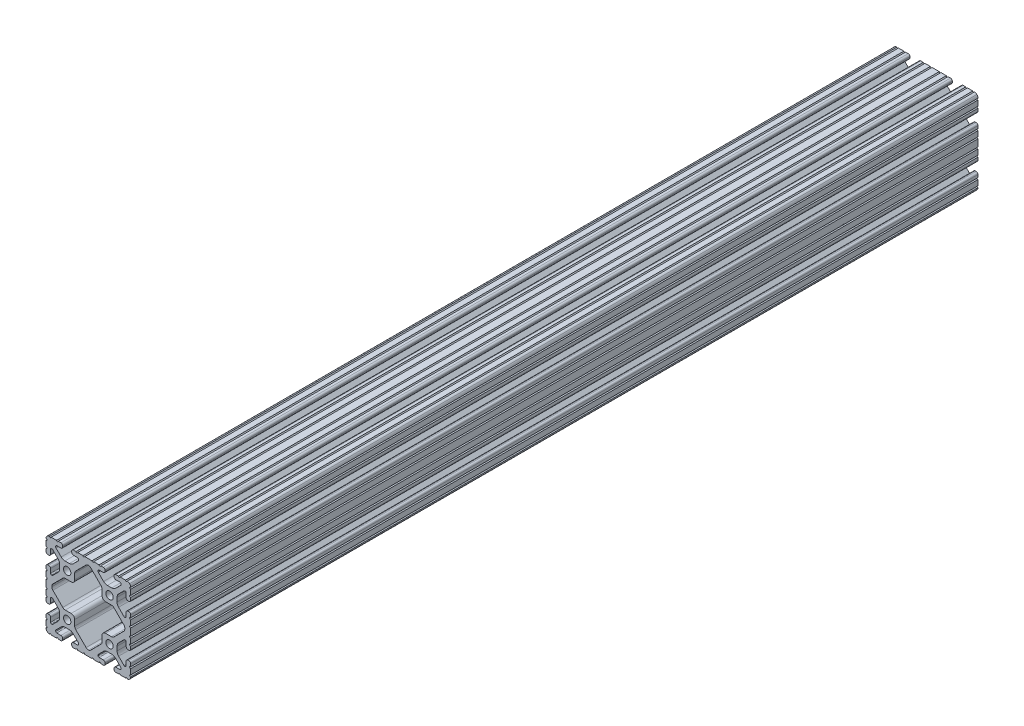
SolidWorks part; units mm, degrees
ref_plane "Front Plane" through (0, 0, 0) normal (0, 0, 1) x (1, 0, 0)
ref_plane "Top Plane" through (0, 0, 0) normal (0, 1, 0) x (1, 0, 0)
ref_plane "Right Plane" through (0, 0, 0) normal (1, 0, 0) x (0, 0, -1)
sketch "Sketch1" plane through (0, 0, 0) normal (0, 0, 1) x (1, 0, 0)
  line L0 (0, 38.1) -> (0, -38.1) construction
  line L1 (-38.1, -38.1) -> (38.1, -38.1) construction
  line L2 (-38.1, -38.1) -> (-38.1, 38.1) construction
  line L3 (-38.1, 38.1) -> (38.1, 38.1) construction
  line L4 (38.1, -38.1) -> (38.1, 38.1) construction
  line L5 (0, 38.1) -> (0, -38.1) construction
  line L6 (-38.1, 0) -> (38.1, 0) construction
  line L7 (-19.05, 19.05) -> (19.05, 19.05) construction
  line L8 (-19.05, 19.05) -> (-19.05, -19.05) construction
  line L9 (-19.05, -19.05) -> (19.05, -19.05) construction
  line L10 (19.05, 19.05) -> (19.05, -19.05) construction
  line L11 (-23.114, 38.1) -> (-23.114, -38.1) construction
  line L12 (-23.114, -38.1) -> (-14.986, 38.1) construction
  line L13 (-14.986, 38.1) -> (-14.986, -38.1) construction
  circle A0 centre (19.05, 19.05) radius 3.3274
  point P0 (0, 0)
  point P9 (0, 0)
  point P12 (-19.05, 0)
  line B0 (-11.3637, -22.8433) -> (-2.0515, -32.1555)
  line B1 (-12.2936, -15.4686) -> (-12.2936, -20.5983)
  line B2 (-20.769, -12.2936) -> (-15.4686, -12.2936)
  line B3 (-31.9021, -2.4756) -> (-23.0141, -11.3637)
  line B4 (-23.0141, 11.3637) -> (-31.9021, 2.4756)
  line B5 (-15.4686, 12.2936) -> (-20.769, 12.2936)
  line B6 (-12.2936, 20.5983) -> (-12.2936, 15.4686)
  line B7 (-2.0515, 32.1555) -> (-11.3637, 22.8433)
  line B8 (11.3637, 22.8433) -> (2.0515, 32.1555)
  line B9 (12.2936, 15.4686) -> (12.2936, 20.5983)
  line B10 (20.769, 12.2936) -> (15.4686, 12.2936)
  line B11 (31.9021, 2.4756) -> (23.0141, 11.3637)
  line B12 (23.0141, -11.3637) -> (31.9021, -2.4756)
  line B13 (15.4686, -12.2936) -> (20.769, -12.2936)
  line B14 (12.2936, -20.5983) -> (12.2936, -15.4686)
  line B15 (2.0515, -32.1555) -> (11.3637, -22.8433)
  line B16 (-4.7773, 38.1) -> (-9.6053, 38.1)
  line B17 (-11.1289, 38.1) -> (-13.4112, 38.1)
  line B18 (-14.986, 36.5252) -> (-14.986, 35.6108)
  line B19 (-13.4112, 34.036) -> (-9.652, 34.036)
  line B20 (-8.763, 33.147) -> (-8.763, 32.4935)
  line B21 (-9.0234, 31.8649) -> (-13.6907, 27.1976)
  line B22 (-17.0493, 25.8064) -> (-21.0507, 25.8064)
  line B23 (-24.4093, 27.1976) -> (-29.1002, 31.8885)
  line B24 (-29.337, 32.7207) -> (-29.337, 33.147)
  line B25 (-28.448, 34.036) -> (-24.6888, 34.036)
  line B26 (-23.114, 35.6108) -> (-23.114, 36.5252)
  line B27 (-24.6888, 38.1) -> (-27.0772, 38.1)
  line B28 (-28.6011, 38.1) -> (-33.4288, 38.1)
  line B29 (-38.1, 33.373) -> (-38.1, 28.5453)
  line B30 (-38.1, 27.0238) -> (-38.1, 24.6302)
  line B31 (-36.5252, 23.0554) -> (-35.6108, 23.0554)
  line B32 (-34.036, 24.6302) -> (-34.036, 28.448)
  line B33 (-33.147, 29.337) -> (-32.6643, 29.337)
  line B34 (-32.0357, 29.0766) -> (-27.1976, 24.2385)
  line B35 (-25.8064, 20.8799) -> (-25.8064, 17.2201)
  line B36 (-27.1976, 13.8615) -> (-31.9489, 9.1101)
  line B37 (-32.7869, 8.763) -> (-33.0603, 8.763)
  line B38 (-34.036, 9.7387) -> (-34.036, 13.4698)
  line B39 (-35.6108, 15.0446) -> (-36.5252, 15.0446)
  line B40 (-38.1, 13.4698) -> (-38.1, 11.075)
  line B41 (-38.1, 9.552) -> (-38.1, 4.7238)
  line B42 (-38.1, 3.2007) -> (-38.1, -3.2007)
  line B43 (-38.1, -4.7238) -> (-38.1, -9.552)
  line B44 (-38.1, -11.075) -> (-38.1, -13.4698)
  line B45 (-36.5252, -15.0446) -> (-35.6108, -15.0446)
  line B46 (-34.036, -13.4698) -> (-34.036, -9.7387)
  line B47 (-33.0603, -8.763) -> (-32.7869, -8.763)
  line B48 (-31.9489, -9.1101) -> (-27.1976, -13.8615)
  line B49 (-25.8064, -17.2201) -> (-25.8064, -20.8799)
  line B50 (-27.1976, -24.2385) -> (-32.0357, -29.0766)
  line B51 (-32.6643, -29.337) -> (-33.147, -29.337)
  line B52 (-34.036, -28.448) -> (-34.036, -24.6302)
  line B53 (-35.6108, -23.0554) -> (-36.5252, -23.0554)
  line B54 (-38.1, -24.6302) -> (-38.1, -27.0238)
  line B55 (-38.1, -28.5453) -> (-38.1, -33.373)
  line B56 (-33.4288, -38.1) -> (-28.6011, -38.1)
  line B57 (-27.0772, -38.1) -> (-24.6888, -38.1)
  line B58 (-23.114, -36.5252) -> (-23.114, -35.6108)
  line B59 (-24.6888, -34.036) -> (-28.448, -34.036)
  line B60 (-29.337, -33.147) -> (-29.337, -32.7207)
  line B61 (-29.1002, -31.8885) -> (-24.4093, -27.1976)
  line B62 (-21.0507, -25.8064) -> (-17.0493, -25.8064)
  line B63 (-13.6907, -27.1976) -> (-9.0234, -31.8649)
  line B64 (-8.763, -32.4935) -> (-8.763, -33.147)
  line B65 (-9.652, -34.036) -> (-13.4112, -34.036)
  line B66 (-14.986, -35.6108) -> (-14.986, -36.5252)
  line B67 (-13.4112, -38.1) -> (-11.1289, -38.1)
  line B68 (-9.6053, -38.1) -> (-4.7773, -38.1)
  line B69 (-3.2537, -38.1) -> (3.2537, -38.1)
  line B70 (4.7773, -38.1) -> (9.6053, -38.1)
  line B71 (11.1289, -38.1) -> (13.4112, -38.1)
  line B72 (14.986, -36.5252) -> (14.986, -35.6108)
  line B73 (13.4112, -34.036) -> (9.652, -34.036)
  line B74 (8.763, -33.147) -> (8.763, -32.4935)
  line B75 (9.0234, -31.8649) -> (13.6907, -27.1976)
  line B76 (17.0493, -25.8064) -> (21.0507, -25.8064)
  line B77 (24.4093, -27.1976) -> (29.1002, -31.8885)
  line B78 (29.337, -32.7207) -> (29.337, -33.147)
  line B79 (28.448, -34.036) -> (24.6888, -34.036)
  line B80 (23.114, -35.6108) -> (23.114, -36.5252)
  line B81 (24.6888, -38.1) -> (27.0772, -38.1)
  line B82 (28.6011, -38.1) -> (33.4288, -38.1)
  line B83 (38.1, -33.373) -> (38.1, -28.5453)
  line B84 (38.1, -27.0238) -> (38.1, -24.6302)
  line B85 (36.5252, -23.0554) -> (35.6108, -23.0554)
  line B86 (34.036, -24.6302) -> (34.036, -28.448)
  line B87 (33.147, -29.337) -> (32.6643, -29.337)
  line B88 (32.0357, -29.0766) -> (27.1976, -24.2385)
  line B89 (25.8064, -20.8799) -> (25.8064, -17.2201)
  line B90 (27.1976, -13.8615) -> (31.9489, -9.1101)
  line B91 (32.7869, -8.763) -> (33.0603, -8.763)
  line B92 (34.036, -9.7387) -> (34.036, -13.4698)
  line B93 (35.6108, -15.0446) -> (36.5252, -15.0446)
  line B94 (38.1, -13.4698) -> (38.1, -11.075)
  line B95 (38.1, -9.552) -> (38.1, -4.7238)
  line B96 (38.1, -3.2007) -> (38.1, 3.2007)
  line B97 (38.1, 4.7238) -> (38.1, 9.552)
  line B98 (38.1, 11.075) -> (38.1, 13.4698)
  line B99 (36.5252, 15.0446) -> (35.6108, 15.0446)
  line B100 (34.036, 13.4698) -> (34.036, 9.7387)
  line B101 (33.0603, 8.763) -> (32.7869, 8.763)
  line B102 (31.9489, 9.1101) -> (27.1976, 13.8615)
  line B103 (25.8064, 17.2201) -> (25.8064, 20.8799)
  line B104 (27.1976, 24.2385) -> (32.0357, 29.0766)
  line B105 (32.6643, 29.337) -> (33.147, 29.337)
  line B106 (34.036, 28.448) -> (34.036, 24.6302)
  line B107 (35.6108, 23.0554) -> (36.5252, 23.0554)
  line B108 (38.1, 24.6302) -> (38.1, 27.0238)
  line B109 (38.1, 28.5453) -> (38.1, 33.373)
  line B110 (33.4288, 38.1) -> (28.6011, 38.1)
  line B111 (27.0772, 38.1) -> (24.6888, 38.1)
  line B112 (23.114, 36.5252) -> (23.114, 35.6108)
  line B113 (24.6888, 34.036) -> (28.448, 34.036)
  line B114 (29.337, 33.147) -> (29.337, 32.7207)
  line B115 (29.1002, 31.8885) -> (24.4093, 27.1976)
  line B116 (21.0507, 25.8064) -> (17.0493, 25.8064)
  line B117 (13.6907, 27.1976) -> (9.0234, 31.8649)
  line B118 (8.763, 32.4935) -> (8.763, 33.147)
  line B119 (9.652, 34.036) -> (13.4112, 34.036)
  line B120 (14.986, 35.6108) -> (14.986, 36.5252)
  line B121 (13.4112, 38.1) -> (11.1289, 38.1)
  line B122 (9.6053, 38.1) -> (4.7773, 38.1)
  line B123 (3.2537, 38.1) -> (-3.2537, 38.1)
  circle B124 centre (-19.05, 19.05) radius 3.3274
  circle B125 centre (-19.05, -19.05) radius 3.3274
  circle B126 centre (19.05, -19.05) radius 3.3274
  circle B127 centre (19.05, 19.05) radius 3.3274
  arc B128 (0, -33.011) -> (2.0515, -32.1555) centre (-0.0139, -30.09) ccw
  arc B129 (-2.0515, -32.1555) -> (0, -33.011) centre (0.0139, -30.09) ccw
  arc B130 (-12.2936, -20.5983) -> (-11.3637, -22.8433) centre (-9.1186, -20.5983) ccw
  arc B131 (-12.2936, -15.4686) -> (-15.4686, -12.2936) centre (-15.4686, -15.4686) ccw
  arc B132 (-23.0141, -11.3637) -> (-20.769, -12.2936) centre (-20.769, -9.1186) ccw
  arc B133 (-32.7287, 0) -> (-31.9021, -2.4756) centre (-29.8367, -0.4102) ccw
  arc B134 (-31.9021, 2.4756) -> (-32.7287, 0) centre (-29.8367, 0.4102) ccw
  arc B135 (-20.769, 12.2936) -> (-23.0141, 11.3637) centre (-20.769, 9.1186) ccw
  arc B136 (-15.4686, 12.2936) -> (-12.2936, 15.4686) centre (-15.4686, 15.4686) ccw
  arc B137 (-11.3637, 22.8433) -> (-12.2936, 20.5983) centre (-9.1186, 20.5983) ccw
  arc B138 (0, 33.011) -> (-2.0515, 32.1555) centre (0.0139, 30.09) ccw
  arc B139 (2.0515, 32.1555) -> (0, 33.011) centre (-0.0139, 30.09) ccw
  arc B140 (12.2936, 20.5983) -> (11.3637, 22.8433) centre (9.1186, 20.5983) ccw
  arc B141 (12.2936, 15.4686) -> (15.4686, 12.2936) centre (15.4686, 15.4686) ccw
  arc B142 (23.0141, 11.3637) -> (20.769, 12.2936) centre (20.769, 9.1186) ccw
  arc B143 (32.7287, 0) -> (31.9021, 2.4756) centre (29.8367, 0.4102) ccw
  arc B144 (31.9021, -2.4756) -> (32.7287, 0) centre (29.8367, -0.4102) ccw
  arc B145 (20.769, -12.2936) -> (23.0141, -11.3637) centre (20.769, -9.1186) ccw
  arc B146 (15.4686, -12.2936) -> (12.2936, -15.4686) centre (15.4686, -15.4686) ccw
  arc B147 (11.3637, -22.8433) -> (12.2936, -20.5983) centre (9.1186, -20.5983) ccw
  arc B148 (-4.7773, 38.1) -> (-3.2537, 38.1) centre (-4.0155, 38.0824) ccw
  arc B149 (-11.1289, 38.1) -> (-9.6053, 38.1) centre (-10.3671, 38.0824) ccw
  arc B150 (-13.4112, 38.1) -> (-14.986, 36.5252) centre (-13.4112, 36.5252) ccw
  arc B151 (-14.986, 35.6108) -> (-13.4112, 34.036) centre (-13.4112, 35.6108) ccw
  arc B152 (-8.763, 33.147) -> (-9.652, 34.036) centre (-9.652, 33.147) ccw
  arc B153 (-9.0234, 31.8649) -> (-8.763, 32.4935) centre (-9.652, 32.4935) ccw
  arc B154 (-17.0493, 25.8064) -> (-13.6907, 27.1976) centre (-17.0493, 30.5562) ccw
  arc B155 (-24.4093, 27.1976) -> (-21.0507, 25.8064) centre (-21.0507, 30.5562) ccw
  arc B156 (-29.337, 32.7207) -> (-29.1002, 31.8885) centre (-28.4716, 32.5172) ccw
  arc B157 (-28.448, 34.036) -> (-29.337, 33.147) centre (-28.448, 33.147) ccw
  arc B158 (-24.6888, 34.036) -> (-23.114, 35.6108) centre (-24.6888, 35.6108) ccw
  arc B159 (-23.114, 36.5252) -> (-24.6888, 38.1) centre (-24.6888, 36.5252) ccw
  arc B160 (-28.6011, 38.1) -> (-27.0772, 38.1) centre (-27.8392, 38.0824) ccw
  arc B161 (-34.9527, 38.1) -> (-33.4288, 38.1) centre (-34.1907, 38.0824) ccw
  arc B162 (-34.9527, 38.1) -> (-37.0861, 37.1826) centre (-34.8521, 34.9266) ccw
  arc B163 (-37.0861, 37.1826) -> (-38.1, 34.8455) centre (-34.925, 34.8566) ccw
  arc B164 (-38.1, 33.373) -> (-38.1, 34.8455) centre (-37.9035, 34.1092) ccw
  arc B165 (-38.1, 27.0238) -> (-38.1, 28.5453) centre (-37.9035, 27.7845) ccw
  arc B166 (-38.1, 24.6302) -> (-36.5252, 23.0554) centre (-36.5252, 24.6302) ccw
  arc B167 (-35.6108, 23.0554) -> (-34.036, 24.6302) centre (-35.6108, 24.6302) ccw
  arc B168 (-33.147, 29.337) -> (-34.036, 28.448) centre (-33.147, 28.448) ccw
  arc B169 (-32.0357, 29.0766) -> (-32.6643, 29.337) centre (-32.6643, 28.448) ccw
  arc B170 (-25.8064, 20.8799) -> (-27.1976, 24.2385) centre (-30.5562, 20.8799) ccw
  arc B171 (-27.1976, 13.8615) -> (-25.8064, 17.2201) centre (-30.5562, 17.2201) ccw
  arc B172 (-32.7869, 8.763) -> (-31.9489, 9.1101) centre (-32.7869, 9.9481) ccw
  arc B173 (-34.036, 9.7387) -> (-33.0603, 8.763) centre (-33.0603, 9.7387) ccw
  arc B174 (-34.036, 13.4698) -> (-35.6108, 15.0446) centre (-35.6108, 13.4698) ccw
  arc B175 (-36.5252, 15.0446) -> (-38.1, 13.4698) centre (-36.5252, 13.4698) ccw
  arc B176 (-38.1, 9.552) -> (-38.1, 11.075) centre (-37.9035, 10.3135) ccw
  arc B177 (-38.1, 3.2007) -> (-38.1, 4.7238) centre (-37.9035, 3.9622) ccw
  arc B178 (-38.1, -4.7238) -> (-38.1, -3.2007) centre (-37.9035, -3.9622) ccw
  arc B179 (-38.1, -11.075) -> (-38.1, -9.552) centre (-37.9035, -10.3135) ccw
  arc B180 (-38.1, -13.4698) -> (-36.5252, -15.0446) centre (-36.5252, -13.4698) ccw
  arc B181 (-35.6108, -15.0446) -> (-34.036, -13.4698) centre (-35.6108, -13.4698) ccw
  arc B182 (-33.0603, -8.763) -> (-34.036, -9.7387) centre (-33.0603, -9.7387) ccw
  arc B183 (-31.9489, -9.1101) -> (-32.7869, -8.763) centre (-32.7869, -9.9481) ccw
  arc B184 (-25.8064, -17.2201) -> (-27.1976, -13.8615) centre (-30.5562, -17.2201) ccw
  arc B185 (-27.1976, -24.2385) -> (-25.8064, -20.8799) centre (-30.5562, -20.8799) ccw
  arc B186 (-32.6643, -29.337) -> (-32.0357, -29.0766) centre (-32.6643, -28.448) ccw
  arc B187 (-34.036, -28.448) -> (-33.147, -29.337) centre (-33.147, -28.448) ccw
  arc B188 (-34.036, -24.6302) -> (-35.6108, -23.0554) centre (-35.6108, -24.6302) ccw
  arc B189 (-36.5252, -23.0554) -> (-38.1, -24.6302) centre (-36.5252, -24.6302) ccw
  arc B190 (-38.1, -28.5453) -> (-38.1, -27.0238) centre (-37.9035, -27.7845) ccw
  arc B191 (-38.1, -34.8455) -> (-38.1, -33.373) centre (-37.9035, -34.1092) ccw
  arc B192 (-38.1, -34.8455) -> (-37.0861, -37.1826) centre (-34.925, -34.8566) ccw
  arc B193 (-37.0861, -37.1826) -> (-34.9527, -38.1) centre (-34.8521, -34.9266) ccw
  arc B194 (-33.4288, -38.1) -> (-34.9527, -38.1) centre (-34.1907, -38.0824) ccw
  arc B195 (-27.0772, -38.1) -> (-28.6011, -38.1) centre (-27.8392, -38.0824) ccw
  arc B196 (-24.6888, -38.1) -> (-23.114, -36.5252) centre (-24.6888, -36.5252) ccw
  arc B197 (-23.114, -35.6108) -> (-24.6888, -34.036) centre (-24.6888, -35.6108) ccw
  arc B198 (-29.337, -33.147) -> (-28.448, -34.036) centre (-28.448, -33.147) ccw
  arc B199 (-29.1002, -31.8885) -> (-29.337, -32.7207) centre (-28.4716, -32.5172) ccw
  arc B200 (-21.0507, -25.8064) -> (-24.4093, -27.1976) centre (-21.0507, -30.5562) ccw
  arc B201 (-13.6907, -27.1976) -> (-17.0493, -25.8064) centre (-17.0493, -30.5562) ccw
  arc B202 (-8.763, -32.4935) -> (-9.0234, -31.8649) centre (-9.652, -32.4935) ccw
  arc B203 (-9.652, -34.036) -> (-8.763, -33.147) centre (-9.652, -33.147) ccw
  arc B204 (-13.4112, -34.036) -> (-14.986, -35.6108) centre (-13.4112, -35.6108) ccw
  arc B205 (-14.986, -36.5252) -> (-13.4112, -38.1) centre (-13.4112, -36.5252) ccw
  arc B206 (-9.6053, -38.1) -> (-11.1289, -38.1) centre (-10.3671, -38.0824) ccw
  arc B207 (-3.2537, -38.1) -> (-4.7773, -38.1) centre (-4.0155, -38.0824) ccw
  arc B208 (4.7773, -38.1) -> (3.2537, -38.1) centre (4.0155, -38.0824) ccw
  arc B209 (11.1289, -38.1) -> (9.6053, -38.1) centre (10.3671, -38.0824) ccw
  arc B210 (13.4112, -38.1) -> (14.986, -36.5252) centre (13.4112, -36.5252) ccw
  arc B211 (14.986, -35.6108) -> (13.4112, -34.036) centre (13.4112, -35.6108) ccw
  arc B212 (8.763, -33.147) -> (9.652, -34.036) centre (9.652, -33.147) ccw
  arc B213 (9.0234, -31.8649) -> (8.763, -32.4935) centre (9.652, -32.4935) ccw
  arc B214 (17.0493, -25.8064) -> (13.6907, -27.1976) centre (17.0493, -30.5562) ccw
  arc B215 (24.4093, -27.1976) -> (21.0507, -25.8064) centre (21.0507, -30.5562) ccw
  arc B216 (29.337, -32.7207) -> (29.1002, -31.8885) centre (28.4716, -32.5172) ccw
  arc B217 (28.448, -34.036) -> (29.337, -33.147) centre (28.448, -33.147) ccw
  arc B218 (24.6888, -34.036) -> (23.114, -35.6108) centre (24.6888, -35.6108) ccw
  arc B219 (23.114, -36.5252) -> (24.6888, -38.1) centre (24.6888, -36.5252) ccw
  arc B220 (28.6011, -38.1) -> (27.0772, -38.1) centre (27.8392, -38.0824) ccw
  arc B221 (34.9527, -38.1) -> (33.4288, -38.1) centre (34.1907, -38.0824) ccw
  arc B222 (34.9527, -38.1) -> (37.0861, -37.1826) centre (34.8521, -34.9266) ccw
  arc B223 (37.0861, -37.1826) -> (38.1, -34.8455) centre (34.925, -34.8566) ccw
  arc B224 (38.1, -33.373) -> (38.1, -34.8455) centre (37.9035, -34.1092) ccw
  arc B225 (38.1, -27.0238) -> (38.1, -28.5453) centre (37.9035, -27.7845) ccw
  arc B226 (38.1, -24.6302) -> (36.5252, -23.0554) centre (36.5252, -24.6302) ccw
  arc B227 (35.6108, -23.0554) -> (34.036, -24.6302) centre (35.6108, -24.6302) ccw
  arc B228 (33.147, -29.337) -> (34.036, -28.448) centre (33.147, -28.448) ccw
  arc B229 (32.0357, -29.0766) -> (32.6643, -29.337) centre (32.6643, -28.448) ccw
  arc B230 (25.8064, -20.8799) -> (27.1976, -24.2385) centre (30.5562, -20.8799) ccw
  arc B231 (27.1976, -13.8615) -> (25.8064, -17.2201) centre (30.5562, -17.2201) ccw
  arc B232 (32.7869, -8.763) -> (31.9489, -9.1101) centre (32.7869, -9.9481) ccw
  arc B233 (34.036, -9.7387) -> (33.0603, -8.763) centre (33.0603, -9.7387) ccw
  arc B234 (34.036, -13.4698) -> (35.6108, -15.0446) centre (35.6108, -13.4698) ccw
  arc B235 (36.5252, -15.0446) -> (38.1, -13.4698) centre (36.5252, -13.4698) ccw
  arc B236 (38.1, -9.552) -> (38.1, -11.075) centre (37.9035, -10.3135) ccw
  arc B237 (38.1, -3.2007) -> (38.1, -4.7238) centre (37.9035, -3.9622) ccw
  arc B238 (38.1, 4.7238) -> (38.1, 3.2007) centre (37.9035, 3.9622) ccw
  arc B239 (38.1, 11.075) -> (38.1, 9.552) centre (37.9035, 10.3135) ccw
  arc B240 (38.1, 13.4698) -> (36.5252, 15.0446) centre (36.5252, 13.4698) ccw
  arc B241 (35.6108, 15.0446) -> (34.036, 13.4698) centre (35.6108, 13.4698) ccw
  arc B242 (33.0603, 8.763) -> (34.036, 9.7387) centre (33.0603, 9.7387) ccw
  arc B243 (31.9489, 9.1101) -> (32.7869, 8.763) centre (32.7869, 9.9481) ccw
  arc B244 (25.8064, 17.2201) -> (27.1976, 13.8615) centre (30.5562, 17.2201) ccw
  arc B245 (27.1976, 24.2385) -> (25.8064, 20.8799) centre (30.5562, 20.8799) ccw
  arc B246 (32.6643, 29.337) -> (32.0357, 29.0766) centre (32.6643, 28.448) ccw
  arc B247 (34.036, 28.448) -> (33.147, 29.337) centre (33.147, 28.448) ccw
  arc B248 (34.036, 24.6302) -> (35.6108, 23.0554) centre (35.6108, 24.6302) ccw
  arc B249 (36.5252, 23.0554) -> (38.1, 24.6302) centre (36.5252, 24.6302) ccw
  arc B250 (38.1, 28.5453) -> (38.1, 27.0238) centre (37.9035, 27.7845) ccw
  arc B251 (38.1, 34.8455) -> (38.1, 33.373) centre (37.9035, 34.1092) ccw
  arc B252 (38.1, 34.8455) -> (37.0861, 37.1826) centre (34.925, 34.8566) ccw
  arc B253 (37.0861, 37.1826) -> (34.9527, 38.1) centre (34.8521, 34.9266) ccw
  arc B254 (33.4288, 38.1) -> (34.9527, 38.1) centre (34.1907, 38.0824) ccw
  arc B255 (27.0772, 38.1) -> (28.6011, 38.1) centre (27.8392, 38.0824) ccw
  arc B256 (24.6888, 38.1) -> (23.114, 36.5252) centre (24.6888, 36.5252) ccw
  arc B257 (23.114, 35.6108) -> (24.6888, 34.036) centre (24.6888, 35.6108) ccw
  arc B258 (29.337, 33.147) -> (28.448, 34.036) centre (28.448, 33.147) ccw
  arc B259 (29.1002, 31.8885) -> (29.337, 32.7207) centre (28.4716, 32.5172) ccw
  arc B260 (21.0507, 25.8064) -> (24.4093, 27.1976) centre (21.0507, 30.5562) ccw
  arc B261 (13.6907, 27.1976) -> (17.0493, 25.8064) centre (17.0493, 30.5562) ccw
  arc B262 (8.763, 32.4935) -> (9.0234, 31.8649) centre (9.652, 32.4935) ccw
  arc B263 (9.652, 34.036) -> (8.763, 33.147) centre (9.652, 33.147) ccw
  arc B264 (13.4112, 34.036) -> (14.986, 35.6108) centre (13.4112, 35.6108) ccw
  arc B265 (14.986, 36.5252) -> (13.4112, 38.1) centre (13.4112, 36.5252) ccw
  arc B266 (9.6053, 38.1) -> (11.1289, 38.1) centre (10.3671, 38.0824) ccw
  arc B267 (3.2537, 38.1) -> (4.7773, 38.1) centre (4.0155, 38.0824) ccw
  dimension "Center Hole Diameter" = 6.6548
  dimension "Rail Width" = 76.2
  dimension "Rail Height" = 76.2
  dimension "T-Slot Width" = 8.128
sketch_block_instance "Block1-1"
sketch_block "Block1"
sketch "Sketch2" plane through (0, 0, 0) normal (1, 0, 0) x (0, 0, -1)
  line L0 (-381, 0) -> (381, 0) construction
  line L1 (-381, 38.1) -> (-381, -38.1) construction
  line L2 (-381, -38.1) -> (381, -38.1) construction
  line L3 (381, -38.1) -> (381, 38.1) construction
  line L4 (-279.4, 0) -> (-279.4, 38.1) construction
  line L5 (-279.4, 38.1) -> (279.4, 38.1) construction
  line L6 (279.4, 38.1) -> (279.4, 0) construction
  point P5 (279.4, 0)
  point P10 (-279.4, 0)
  dimension "D1" = 101.6
  dimension "Length" = 762
  dimension "D2" = 101.6
sketch "Sketch3" plane through (0, 0, 0) normal (0, 0, 1) x (1, 0, 0)
  line L0 (-11.3637, -22.8433) -> (-2.0515, -32.1555) construction
  line L1 (-12.2936, -15.4686) -> (-12.2936, -20.5983) construction
  line L2 (-20.769, -12.2936) -> (-15.4686, -12.2936) construction
  line L3 (-31.9021, -2.4756) -> (-23.0141, -11.3637) construction
  line L4 (-23.0141, 11.3637) -> (-31.9021, 2.4756) construction
  line L5 (-15.4686, 12.2936) -> (-20.769, 12.2936) construction
  line L6 (-12.2936, 20.5983) -> (-12.2936, 15.4686) construction
  line L7 (-2.0515, 32.1555) -> (-11.3637, 22.8433) construction
  line L8 (11.3637, 22.8433) -> (2.0515, 32.1555) construction
  line L9 (12.2936, 15.4686) -> (12.2936, 20.5983) construction
  line L10 (20.769, 12.2936) -> (15.4686, 12.2936) construction
  line L11 (31.9021, 2.4756) -> (23.0141, 11.3637) construction
  line L12 (23.0141, -11.3637) -> (31.9021, -2.4756) construction
  line L13 (15.4686, -12.2936) -> (20.769, -12.2936) construction
  line L14 (12.2936, -20.5983) -> (12.2936, -15.4686) construction
  line L15 (2.0515, -32.1555) -> (11.3637, -22.8433) construction
  line L16 (34.036, 28.448) -> (34.036, 24.6302) construction
  line L17 (35.6108, 23.0554) -> (36.5252, 23.0554) construction
  line L18 (38.1, 24.6302) -> (38.1, 27.0238) construction
  line L19 (38.1, 28.5453) -> (38.1, 33.373) construction
  line L20 (33.4288, 38.1) -> (28.6011, 38.1) construction
  line L21 (27.0772, 38.1) -> (24.6888, 38.1) construction
  line L22 (23.114, 36.5252) -> (23.114, 35.6108) construction
  line L23 (24.6888, 34.036) -> (28.448, 34.036) construction
  line L24 (29.337, 33.147) -> (29.337, 32.7207) construction
  line L25 (29.1002, 31.8885) -> (24.4093, 27.1976) construction
  line L26 (21.0507, 25.8064) -> (17.0493, 25.8064) construction
  line L27 (13.6907, 27.1976) -> (9.0234, 31.8649) construction
  line L28 (8.763, 32.4935) -> (8.763, 33.147) construction
  line L29 (9.652, 34.036) -> (13.4112, 34.036) construction
  line L30 (14.986, 35.6108) -> (14.986, 36.5252) construction
  line L31 (13.4112, 38.1) -> (11.1289, 38.1) construction
  line L32 (9.6053, 38.1) -> (4.7773, 38.1) construction
  line L33 (3.2537, 38.1) -> (-3.2537, 38.1) construction
  line L34 (-4.7773, 38.1) -> (-9.6053, 38.1) construction
  line L35 (-11.1289, 38.1) -> (-13.4112, 38.1) construction
  line L36 (-14.986, 36.5252) -> (-14.986, 35.6108) construction
  line L37 (-13.4112, 34.036) -> (-9.652, 34.036) construction
  line L38 (-8.763, 33.147) -> (-8.763, 32.4935) construction
  line L39 (-9.0234, 31.8649) -> (-13.6907, 27.1976) construction
  line L40 (-17.0493, 25.8064) -> (-21.0507, 25.8064) construction
  line L41 (-24.4093, 27.1976) -> (-29.1002, 31.8885) construction
  line L42 (-29.337, 32.7207) -> (-29.337, 33.147) construction
  line L43 (-28.448, 34.036) -> (-24.6888, 34.036) construction
  line L44 (-23.114, 35.6108) -> (-23.114, 36.5252) construction
  line L45 (-24.6888, 38.1) -> (-27.0772, 38.1) construction
  line L46 (-28.6011, 38.1) -> (-33.4288, 38.1) construction
  line L47 (-38.1, 33.373) -> (-38.1, 28.5453) construction
  line L48 (-38.1, 27.0238) -> (-38.1, 24.6302) construction
  line L49 (-36.5252, 23.0554) -> (-35.6108, 23.0554) construction
  line L50 (-34.036, 24.6302) -> (-34.036, 28.448) construction
  line L51 (-33.147, 29.337) -> (-32.6643, 29.337) construction
  line L52 (-32.0357, 29.0766) -> (-27.1976, 24.2385) construction
  line L53 (-25.8064, 20.8799) -> (-25.8064, 17.2201) construction
  line L54 (-27.1976, 13.8615) -> (-31.9489, 9.1101) construction
  line L55 (-32.7869, 8.763) -> (-33.0603, 8.763) construction
  line L56 (-34.036, 9.7387) -> (-34.036, 13.4698) construction
  line L57 (-35.6108, 15.0446) -> (-36.5252, 15.0446) construction
  line L58 (-38.1, 13.4698) -> (-38.1, 11.075) construction
  line L59 (-38.1, 9.552) -> (-38.1, 4.7238) construction
  line L60 (-38.1, 3.2007) -> (-38.1, -3.2007) construction
  line L61 (-38.1, -4.7238) -> (-38.1, -9.552) construction
  line L62 (-38.1, -11.075) -> (-38.1, -13.4698) construction
  line L63 (-36.5252, -15.0446) -> (-35.6108, -15.0446) construction
  line L64 (-34.036, -13.4698) -> (-34.036, -9.7387) construction
  line L65 (-33.0603, -8.763) -> (-32.7869, -8.763) construction
  line L66 (-31.9489, -9.1101) -> (-27.1976, -13.8615) construction
  line L67 (-25.8064, -17.2201) -> (-25.8064, -20.8799) construction
  line L68 (-27.1976, -24.2385) -> (-32.0357, -29.0766) construction
  line L69 (-32.6643, -29.337) -> (-33.147, -29.337) construction
  line L70 (-34.036, -28.448) -> (-34.036, -24.6302) construction
  line L71 (-35.6108, -23.0554) -> (-36.5252, -23.0554) construction
  line L72 (-38.1, -24.6302) -> (-38.1, -27.0238) construction
  line L73 (-38.1, -28.5453) -> (-38.1, -33.373) construction
  line L74 (-33.4288, -38.1) -> (-28.6011, -38.1) construction
  line L75 (-27.0772, -38.1) -> (-24.6888, -38.1) construction
  line L76 (-23.114, -36.5252) -> (-23.114, -35.6108) construction
  line L77 (-24.6888, -34.036) -> (-28.448, -34.036) construction
  line L78 (-29.337, -33.147) -> (-29.337, -32.7207) construction
  line L79 (-29.1002, -31.8885) -> (-24.4093, -27.1976) construction
  line L80 (-21.0507, -25.8064) -> (-17.0493, -25.8064) construction
  line L81 (-13.6907, -27.1976) -> (-9.0234, -31.8649) construction
  line L82 (-8.763, -32.4935) -> (-8.763, -33.147) construction
  line L83 (-9.652, -34.036) -> (-13.4112, -34.036) construction
  line L84 (-14.986, -35.6108) -> (-14.986, -36.5252) construction
  line L85 (-13.4112, -38.1) -> (-11.1289, -38.1) construction
  line L86 (-9.6053, -38.1) -> (-4.7773, -38.1) construction
  line L87 (-3.2537, -38.1) -> (3.2537, -38.1) construction
  line L88 (4.7773, -38.1) -> (9.6053, -38.1) construction
  line L89 (11.1289, -38.1) -> (13.4112, -38.1) construction
  line L90 (14.986, -36.5252) -> (14.986, -35.6108) construction
  line L91 (13.4112, -34.036) -> (9.652, -34.036) construction
  line L92 (8.763, -33.147) -> (8.763, -32.4935) construction
  line L93 (9.0234, -31.8649) -> (13.6907, -27.1976) construction
  line L94 (17.0493, -25.8064) -> (21.0507, -25.8064) construction
  line L95 (24.4093, -27.1976) -> (29.1002, -31.8885) construction
  line L96 (29.337, -32.7207) -> (29.337, -33.147) construction
  line L97 (28.448, -34.036) -> (24.6888, -34.036) construction
  line L98 (23.114, -35.6108) -> (23.114, -36.5252) construction
  line L99 (24.6888, -38.1) -> (27.0772, -38.1) construction
  line L100 (28.6011, -38.1) -> (33.4288, -38.1) construction
  line L101 (38.1, -33.373) -> (38.1, -28.5453) construction
  line L102 (38.1, -27.0238) -> (38.1, -24.6302) construction
  line L103 (36.5252, -23.0554) -> (35.6108, -23.0554) construction
  line L104 (34.036, -24.6302) -> (34.036, -28.448) construction
  line L105 (33.147, -29.337) -> (32.6643, -29.337) construction
  line L106 (32.0357, -29.0766) -> (27.1976, -24.2385) construction
  line L107 (25.8064, -20.8799) -> (25.8064, -17.2201) construction
  line L108 (27.1976, -13.8615) -> (31.9489, -9.1101) construction
  line L109 (32.7869, -8.763) -> (33.0603, -8.763) construction
  line L110 (34.036, -9.7387) -> (34.036, -13.4698) construction
  line L111 (35.6108, -15.0446) -> (36.5252, -15.0446) construction
  line L112 (38.1, -13.4698) -> (38.1, -11.075) construction
  line L113 (38.1, -9.552) -> (38.1, -4.7238) construction
  line L114 (38.1, -3.2007) -> (38.1, 3.2007) construction
  line L115 (38.1, 4.7238) -> (38.1, 9.552) construction
  line L116 (38.1, 11.075) -> (38.1, 13.4698) construction
  line L117 (36.5252, 15.0446) -> (35.6108, 15.0446) construction
  line L118 (34.036, 13.4698) -> (34.036, 9.7387) construction
  line L119 (33.0603, 8.763) -> (32.7869, 8.763) construction
  line L120 (31.9489, 9.1101) -> (27.1976, 13.8615) construction
  line L121 (25.8064, 17.2201) -> (25.8064, 20.8799) construction
  line L122 (27.1976, 24.2385) -> (32.0357, 29.0766) construction
  line L123 (32.6643, 29.337) -> (33.147, 29.337) construction
  line L124 (-11.3637, -22.8433) -> (-2.0515, -32.1555)
  line L125 (-12.2936, -15.4686) -> (-12.2936, -20.5983)
  line L126 (-20.769, -12.2936) -> (-15.4686, -12.2936)
  line L127 (-31.9021, -2.4756) -> (-23.0141, -11.3637)
  line L128 (-23.0141, 11.3637) -> (-31.9021, 2.4756)
  line L129 (-15.4686, 12.2936) -> (-20.769, 12.2936)
  line L130 (-12.2936, 20.5983) -> (-12.2936, 15.4686)
  line L131 (-2.0515, 32.1555) -> (-11.3637, 22.8433)
  line L132 (11.3637, 22.8433) -> (2.0515, 32.1555)
  line L133 (12.2936, 15.4686) -> (12.2936, 20.5983)
  line L134 (20.769, 12.2936) -> (15.4686, 12.2936)
  line L135 (31.9021, 2.4756) -> (23.0141, 11.3637)
  line L136 (23.0141, -11.3637) -> (31.9021, -2.4756)
  line L137 (15.4686, -12.2936) -> (20.769, -12.2936)
  line L138 (12.2936, -20.5983) -> (12.2936, -15.4686)
  line L139 (2.0515, -32.1555) -> (11.3637, -22.8433)
  line L140 (34.036, 28.448) -> (34.036, 24.6302)
  line L141 (35.6108, 23.0554) -> (36.5252, 23.0554)
  line L142 (38.1, 24.6302) -> (38.1, 27.0238)
  line L143 (38.1, 28.5453) -> (38.1, 33.373)
  line L144 (33.4288, 38.1) -> (28.6011, 38.1)
  line L145 (27.0772, 38.1) -> (24.6888, 38.1)
  line L146 (23.114, 36.5252) -> (23.114, 35.6108)
  line L147 (24.6888, 34.036) -> (28.448, 34.036)
  line L148 (29.337, 33.147) -> (29.337, 32.7207)
  line L149 (29.1002, 31.8885) -> (24.4093, 27.1976)
  line L150 (21.0507, 25.8064) -> (17.0493, 25.8064)
  line L151 (13.6907, 27.1976) -> (9.0234, 31.8649)
  line L152 (8.763, 32.4935) -> (8.763, 33.147)
  line L153 (9.652, 34.036) -> (13.4112, 34.036)
  line L154 (14.986, 35.6108) -> (14.986, 36.5252)
  line L155 (13.4112, 38.1) -> (11.1289, 38.1)
  line L156 (9.6053, 38.1) -> (4.7773, 38.1)
  line L157 (3.2537, 38.1) -> (-3.2537, 38.1)
  line L158 (-4.7773, 38.1) -> (-9.6053, 38.1)
  line L159 (-11.1289, 38.1) -> (-13.4112, 38.1)
  line L160 (-14.986, 36.5252) -> (-14.986, 35.6108)
  line L161 (-13.4112, 34.036) -> (-9.652, 34.036)
  line L162 (-8.763, 33.147) -> (-8.763, 32.4935)
  line L163 (-9.0234, 31.8649) -> (-13.6907, 27.1976)
  line L164 (-17.0493, 25.8064) -> (-21.0507, 25.8064)
  line L165 (-24.4093, 27.1976) -> (-29.1002, 31.8885)
  line L166 (-29.337, 32.7207) -> (-29.337, 33.147)
  line L167 (-28.448, 34.036) -> (-24.6888, 34.036)
  line L168 (-23.114, 35.6108) -> (-23.114, 36.5252)
  line L169 (-24.6888, 38.1) -> (-27.0772, 38.1)
  line L170 (-28.6011, 38.1) -> (-33.4288, 38.1)
  line L171 (-38.1, 33.373) -> (-38.1, 28.5453)
  line L172 (-38.1, 27.0238) -> (-38.1, 24.6302)
  line L173 (-36.5252, 23.0554) -> (-35.6108, 23.0554)
  line L174 (-34.036, 24.6302) -> (-34.036, 28.448)
  line L175 (-33.147, 29.337) -> (-32.6643, 29.337)
  line L176 (-32.0357, 29.0766) -> (-27.1976, 24.2385)
  line L177 (-25.8064, 20.8799) -> (-25.8064, 17.2201)
  line L178 (-27.1976, 13.8615) -> (-31.9489, 9.1101)
  line L179 (-32.7869, 8.763) -> (-33.0603, 8.763)
  line L180 (-34.036, 9.7387) -> (-34.036, 13.4698)
  line L181 (-35.6108, 15.0446) -> (-36.5252, 15.0446)
  line L182 (-38.1, 13.4698) -> (-38.1, 11.075)
  line L183 (-38.1, 9.552) -> (-38.1, 4.7238)
  line L184 (-38.1, 3.2007) -> (-38.1, -3.2007)
  line L185 (-38.1, -4.7238) -> (-38.1, -9.552)
  line L186 (-38.1, -11.075) -> (-38.1, -13.4698)
  line L187 (-36.5252, -15.0446) -> (-35.6108, -15.0446)
  line L188 (-34.036, -13.4698) -> (-34.036, -9.7387)
  line L189 (-33.0603, -8.763) -> (-32.7869, -8.763)
  line L190 (-31.9489, -9.1101) -> (-27.1976, -13.8615)
  line L191 (-25.8064, -17.2201) -> (-25.8064, -20.8799)
  line L192 (-27.1976, -24.2385) -> (-32.0357, -29.0766)
  line L193 (-32.6643, -29.337) -> (-33.147, -29.337)
  line L194 (-34.036, -28.448) -> (-34.036, -24.6302)
  line L195 (-35.6108, -23.0554) -> (-36.5252, -23.0554)
  line L196 (-38.1, -24.6302) -> (-38.1, -27.0238)
  line L197 (-38.1, -28.5453) -> (-38.1, -33.373)
  line L198 (-33.4288, -38.1) -> (-28.6011, -38.1)
  line L199 (-27.0772, -38.1) -> (-24.6888, -38.1)
  line L200 (-23.114, -36.5252) -> (-23.114, -35.6108)
  line L201 (-24.6888, -34.036) -> (-28.448, -34.036)
  line L202 (-29.337, -33.147) -> (-29.337, -32.7207)
  line L203 (-29.1002, -31.8885) -> (-24.4093, -27.1976)
  line L204 (-21.0507, -25.8064) -> (-17.0493, -25.8064)
  line L205 (-13.6907, -27.1976) -> (-9.0234, -31.8649)
  line L206 (-8.763, -32.4935) -> (-8.763, -33.147)
  line L207 (-9.652, -34.036) -> (-13.4112, -34.036)
  line L208 (-14.986, -35.6108) -> (-14.986, -36.5252)
  line L209 (-13.4112, -38.1) -> (-11.1289, -38.1)
  line L210 (-9.6053, -38.1) -> (-4.7773, -38.1)
  line L211 (-3.2537, -38.1) -> (3.2537, -38.1)
  line L212 (4.7773, -38.1) -> (9.6053, -38.1)
  line L213 (11.1289, -38.1) -> (13.4112, -38.1)
  line L214 (14.986, -36.5252) -> (14.986, -35.6108)
  line L215 (13.4112, -34.036) -> (9.652, -34.036)
  line L216 (8.763, -33.147) -> (8.763, -32.4935)
  line L217 (9.0234, -31.8649) -> (13.6907, -27.1976)
  line L218 (17.0493, -25.8064) -> (21.0507, -25.8064)
  line L219 (24.4093, -27.1976) -> (29.1002, -31.8885)
  line L220 (29.337, -32.7207) -> (29.337, -33.147)
  line L221 (28.448, -34.036) -> (24.6888, -34.036)
  line L222 (23.114, -35.6108) -> (23.114, -36.5252)
  line L223 (24.6888, -38.1) -> (27.0772, -38.1)
  line L224 (28.6011, -38.1) -> (33.4288, -38.1)
  line L225 (38.1, -33.373) -> (38.1, -28.5453)
  line L226 (38.1, -27.0238) -> (38.1, -24.6302)
  line L227 (36.5252, -23.0554) -> (35.6108, -23.0554)
  line L228 (34.036, -24.6302) -> (34.036, -28.448)
  line L229 (33.147, -29.337) -> (32.6643, -29.337)
  line L230 (32.0357, -29.0766) -> (27.1976, -24.2385)
  line L231 (25.8064, -20.8799) -> (25.8064, -17.2201)
  line L232 (27.1976, -13.8615) -> (31.9489, -9.1101)
  line L233 (32.7869, -8.763) -> (33.0603, -8.763)
  line L234 (34.036, -9.7387) -> (34.036, -13.4698)
  line L235 (35.6108, -15.0446) -> (36.5252, -15.0446)
  line L236 (38.1, -13.4698) -> (38.1, -11.075)
  line L237 (38.1, -9.552) -> (38.1, -4.7238)
  line L238 (38.1, -3.2007) -> (38.1, 3.2007)
  line L239 (38.1, 4.7238) -> (38.1, 9.552)
  line L240 (38.1, 11.075) -> (38.1, 13.4698)
  line L241 (36.5252, 15.0446) -> (35.6108, 15.0446)
  line L242 (34.036, 13.4698) -> (34.036, 9.7387)
  line L243 (33.0603, 8.763) -> (32.7869, 8.763)
  line L244 (31.9489, 9.1101) -> (27.1976, 13.8615)
  line L245 (25.8064, 17.2201) -> (25.8064, 20.8799)
  line L246 (27.1976, 24.2385) -> (32.0357, 29.0766)
  line L247 (32.6643, 29.337) -> (33.147, 29.337)
  arc A0 (-2.0515, -32.1555) -> (0, -33.011) centre (0.0139, -30.09) ccw construction
  circle A1 centre (19.05, 19.05) radius 3.3274
  circle A2 centre (19.05, 19.05) radius 3.3274
  arc A3 (-12.2936, -20.5983) -> (-11.3637, -22.8433) centre (-9.1186, -20.5983) ccw construction
  arc A4 (-12.2936, -15.4686) -> (-15.4686, -12.2936) centre (-15.4686, -15.4686) ccw construction
  arc A5 (-23.0141, -11.3637) -> (-20.769, -12.2936) centre (-20.769, -9.1186) ccw construction
  arc A6 (-32.7287, 0) -> (-31.9021, -2.4756) centre (-29.8367, -0.4102) ccw construction
  arc A7 (-31.9021, 2.4756) -> (-32.7287, 0) centre (-29.8367, 0.4102) ccw construction
  arc A8 (-20.769, 12.2936) -> (-23.0141, 11.3637) centre (-20.769, 9.1186) ccw construction
  arc A9 (-15.4686, 12.2936) -> (-12.2936, 15.4686) centre (-15.4686, 15.4686) ccw construction
  arc A10 (-11.3637, 22.8433) -> (-12.2936, 20.5983) centre (-9.1186, 20.5983) ccw construction
  arc A11 (0, 33.011) -> (-2.0515, 32.1555) centre (0.0139, 30.09) ccw construction
  arc A12 (2.0515, 32.1555) -> (0, 33.011) centre (-0.0139, 30.09) ccw construction
  arc A13 (12.2936, 20.5983) -> (11.3637, 22.8433) centre (9.1186, 20.5983) ccw construction
  arc A14 (12.2936, 15.4686) -> (15.4686, 12.2936) centre (15.4686, 15.4686) ccw construction
  arc A15 (23.0141, 11.3637) -> (20.769, 12.2936) centre (20.769, 9.1186) ccw construction
  arc A16 (32.7287, 0) -> (31.9021, 2.4756) centre (29.8367, 0.4102) ccw construction
  arc A17 (31.9021, -2.4756) -> (32.7287, 0) centre (29.8367, -0.4102) ccw construction
  arc A18 (20.769, -12.2936) -> (23.0141, -11.3637) centre (20.769, -9.1186) ccw construction
  arc A19 (15.4686, -12.2936) -> (12.2936, -15.4686) centre (15.4686, -15.4686) ccw construction
  arc A20 (11.3637, -22.8433) -> (12.2936, -20.5983) centre (9.1186, -20.5983) ccw construction
  arc A21 (0, -33.011) -> (2.0515, -32.1555) centre (-0.0139, -30.09) ccw construction
  circle A22 centre (-19.05, 19.05) radius 3.3274 construction
  circle A23 centre (19.05, -19.05) radius 3.3274 construction
  circle A24 centre (-19.05, -19.05) radius 3.3274 construction
  circle A25 centre (19.05, 19.05) radius 3.3274 construction
  arc A26 (34.036, 24.6302) -> (35.6108, 23.0554) centre (35.6108, 24.6302) ccw construction
  arc A27 (36.5252, 23.0554) -> (38.1, 24.6302) centre (36.5252, 24.6302) ccw construction
  arc A28 (38.1, 28.5453) -> (38.1, 27.0238) centre (37.9035, 27.7845) ccw construction
  arc A29 (38.1, 34.8455) -> (38.1, 33.373) centre (37.9035, 34.1092) ccw construction
  arc A30 (38.1, 34.8455) -> (37.0861, 37.1826) centre (34.925, 34.8566) ccw construction
  arc A31 (37.0861, 37.1826) -> (34.9527, 38.1) centre (34.8521, 34.9266) ccw construction
  arc A32 (33.4288, 38.1) -> (34.9527, 38.1) centre (34.1907, 38.0824) ccw construction
  arc A33 (27.0772, 38.1) -> (28.6011, 38.1) centre (27.8392, 38.0824) ccw construction
  arc A34 (24.6888, 38.1) -> (23.114, 36.5252) centre (24.6888, 36.5252) ccw construction
  arc A35 (23.114, 35.6108) -> (24.6888, 34.036) centre (24.6888, 35.6108) ccw construction
  arc A36 (29.337, 33.147) -> (28.448, 34.036) centre (28.448, 33.147) ccw construction
  arc A37 (29.1002, 31.8885) -> (29.337, 32.7207) centre (28.4716, 32.5172) ccw construction
  arc A38 (21.0507, 25.8064) -> (24.4093, 27.1976) centre (21.0507, 30.5562) ccw construction
  arc A39 (13.6907, 27.1976) -> (17.0493, 25.8064) centre (17.0493, 30.5562) ccw construction
  arc A40 (8.763, 32.4935) -> (9.0234, 31.8649) centre (9.652, 32.4935) ccw construction
  arc A41 (9.652, 34.036) -> (8.763, 33.147) centre (9.652, 33.147) ccw construction
  arc A42 (13.4112, 34.036) -> (14.986, 35.6108) centre (13.4112, 35.6108) ccw construction
  arc A43 (14.986, 36.5252) -> (13.4112, 38.1) centre (13.4112, 36.5252) ccw construction
  arc A44 (9.6053, 38.1) -> (11.1289, 38.1) centre (10.3671, 38.0824) ccw construction
  arc A45 (3.2537, 38.1) -> (4.7773, 38.1) centre (4.0155, 38.0824) ccw construction
  arc A46 (-4.7773, 38.1) -> (-3.2537, 38.1) centre (-4.0155, 38.0824) ccw construction
  arc A47 (-11.1289, 38.1) -> (-9.6053, 38.1) centre (-10.3671, 38.0824) ccw construction
  arc A48 (-13.4112, 38.1) -> (-14.986, 36.5252) centre (-13.4112, 36.5252) ccw construction
  arc A49 (-14.986, 35.6108) -> (-13.4112, 34.036) centre (-13.4112, 35.6108) ccw construction
  arc A50 (-8.763, 33.147) -> (-9.652, 34.036) centre (-9.652, 33.147) ccw construction
  arc A51 (-9.0234, 31.8649) -> (-8.763, 32.4935) centre (-9.652, 32.4935) ccw construction
  arc A52 (-17.0493, 25.8064) -> (-13.6907, 27.1976) centre (-17.0493, 30.5562) ccw construction
  arc A53 (-24.4093, 27.1976) -> (-21.0507, 25.8064) centre (-21.0507, 30.5562) ccw construction
  arc A54 (-29.337, 32.7207) -> (-29.1002, 31.8885) centre (-28.4716, 32.5172) ccw construction
  arc A55 (-28.448, 34.036) -> (-29.337, 33.147) centre (-28.448, 33.147) ccw construction
  arc A56 (-24.6888, 34.036) -> (-23.114, 35.6108) centre (-24.6888, 35.6108) ccw construction
  arc A57 (-23.114, 36.5252) -> (-24.6888, 38.1) centre (-24.6888, 36.5252) ccw construction
  arc A58 (-28.6011, 38.1) -> (-27.0772, 38.1) centre (-27.8392, 38.0824) ccw construction
  arc A59 (-34.9527, 38.1) -> (-33.4288, 38.1) centre (-34.1907, 38.0824) ccw construction
  arc A60 (-34.9527, 38.1) -> (-37.0861, 37.1826) centre (-34.8521, 34.9266) ccw construction
  arc A61 (-37.0861, 37.1826) -> (-38.1, 34.8455) centre (-34.925, 34.8566) ccw construction
  arc A62 (-38.1, 33.373) -> (-38.1, 34.8455) centre (-37.9035, 34.1092) ccw construction
  arc A63 (-38.1, 27.0238) -> (-38.1, 28.5453) centre (-37.9035, 27.7845) ccw construction
  arc A64 (-38.1, 24.6302) -> (-36.5252, 23.0554) centre (-36.5252, 24.6302) ccw construction
  arc A65 (-35.6108, 23.0554) -> (-34.036, 24.6302) centre (-35.6108, 24.6302) ccw construction
  arc A66 (-33.147, 29.337) -> (-34.036, 28.448) centre (-33.147, 28.448) ccw construction
  arc A67 (-32.0357, 29.0766) -> (-32.6643, 29.337) centre (-32.6643, 28.448) ccw construction
  arc A68 (-25.8064, 20.8799) -> (-27.1976, 24.2385) centre (-30.5562, 20.8799) ccw construction
  arc A69 (-27.1976, 13.8615) -> (-25.8064, 17.2201) centre (-30.5562, 17.2201) ccw construction
  arc A70 (-32.7869, 8.763) -> (-31.9489, 9.1101) centre (-32.7869, 9.9481) ccw construction
  arc A71 (-34.036, 9.7387) -> (-33.0603, 8.763) centre (-33.0603, 9.7387) ccw construction
  arc A72 (-34.036, 13.4698) -> (-35.6108, 15.0446) centre (-35.6108, 13.4698) ccw construction
  arc A73 (-36.5252, 15.0446) -> (-38.1, 13.4698) centre (-36.5252, 13.4698) ccw construction
  arc A74 (-38.1, 9.552) -> (-38.1, 11.075) centre (-37.9035, 10.3135) ccw construction
  arc A75 (-38.1, 3.2007) -> (-38.1, 4.7238) centre (-37.9035, 3.9622) ccw construction
  arc A76 (-38.1, -4.7238) -> (-38.1, -3.2007) centre (-37.9035, -3.9622) ccw construction
  arc A77 (-38.1, -11.075) -> (-38.1, -9.552) centre (-37.9035, -10.3135) ccw construction
  arc A78 (-38.1, -13.4698) -> (-36.5252, -15.0446) centre (-36.5252, -13.4698) ccw construction
  arc A79 (-35.6108, -15.0446) -> (-34.036, -13.4698) centre (-35.6108, -13.4698) ccw construction
  arc A80 (-33.0603, -8.763) -> (-34.036, -9.7387) centre (-33.0603, -9.7387) ccw construction
  arc A81 (-31.9489, -9.1101) -> (-32.7869, -8.763) centre (-32.7869, -9.9481) ccw construction
  arc A82 (-25.8064, -17.2201) -> (-27.1976, -13.8615) centre (-30.5562, -17.2201) ccw construction
  arc A83 (-27.1976, -24.2385) -> (-25.8064, -20.8799) centre (-30.5562, -20.8799) ccw construction
  arc A84 (-32.6643, -29.337) -> (-32.0357, -29.0766) centre (-32.6643, -28.448) ccw construction
  arc A85 (-34.036, -28.448) -> (-33.147, -29.337) centre (-33.147, -28.448) ccw construction
  arc A86 (-34.036, -24.6302) -> (-35.6108, -23.0554) centre (-35.6108, -24.6302) ccw construction
  arc A87 (-36.5252, -23.0554) -> (-38.1, -24.6302) centre (-36.5252, -24.6302) ccw construction
  arc A88 (-38.1, -28.5453) -> (-38.1, -27.0238) centre (-37.9035, -27.7845) ccw construction
  arc A89 (-38.1, -34.8455) -> (-38.1, -33.373) centre (-37.9035, -34.1092) ccw construction
  arc A90 (-38.1, -34.8455) -> (-37.0861, -37.1826) centre (-34.925, -34.8566) ccw construction
  arc A91 (-37.0861, -37.1826) -> (-34.9527, -38.1) centre (-34.8521, -34.9266) ccw construction
  arc A92 (-33.4288, -38.1) -> (-34.9527, -38.1) centre (-34.1907, -38.0824) ccw construction
  arc A93 (-27.0772, -38.1) -> (-28.6011, -38.1) centre (-27.8392, -38.0824) ccw construction
  arc A94 (-24.6888, -38.1) -> (-23.114, -36.5252) centre (-24.6888, -36.5252) ccw construction
  arc A95 (-23.114, -35.6108) -> (-24.6888, -34.036) centre (-24.6888, -35.6108) ccw construction
  arc A96 (-29.337, -33.147) -> (-28.448, -34.036) centre (-28.448, -33.147) ccw construction
  arc A97 (-29.1002, -31.8885) -> (-29.337, -32.7207) centre (-28.4716, -32.5172) ccw construction
  arc A98 (-21.0507, -25.8064) -> (-24.4093, -27.1976) centre (-21.0507, -30.5562) ccw construction
  arc A99 (-13.6907, -27.1976) -> (-17.0493, -25.8064) centre (-17.0493, -30.5562) ccw construction
  arc A100 (-8.763, -32.4935) -> (-9.0234, -31.8649) centre (-9.652, -32.4935) ccw construction
  arc A101 (-9.652, -34.036) -> (-8.763, -33.147) centre (-9.652, -33.147) ccw construction
  arc A102 (-13.4112, -34.036) -> (-14.986, -35.6108) centre (-13.4112, -35.6108) ccw construction
  arc A103 (-14.986, -36.5252) -> (-13.4112, -38.1) centre (-13.4112, -36.5252) ccw construction
  arc A104 (-9.6053, -38.1) -> (-11.1289, -38.1) centre (-10.3671, -38.0824) ccw construction
  arc A105 (-3.2537, -38.1) -> (-4.7773, -38.1) centre (-4.0155, -38.0824) ccw construction
  arc A106 (4.7773, -38.1) -> (3.2537, -38.1) centre (4.0155, -38.0824) ccw construction
  arc A107 (11.1289, -38.1) -> (9.6053, -38.1) centre (10.3671, -38.0824) ccw construction
  arc A108 (13.4112, -38.1) -> (14.986, -36.5252) centre (13.4112, -36.5252) ccw construction
  arc A109 (14.986, -35.6108) -> (13.4112, -34.036) centre (13.4112, -35.6108) ccw construction
  arc A110 (8.763, -33.147) -> (9.652, -34.036) centre (9.652, -33.147) ccw construction
  arc A111 (9.0234, -31.8649) -> (8.763, -32.4935) centre (9.652, -32.4935) ccw construction
  arc A112 (17.0493, -25.8064) -> (13.6907, -27.1976) centre (17.0493, -30.5562) ccw construction
  arc A113 (24.4093, -27.1976) -> (21.0507, -25.8064) centre (21.0507, -30.5562) ccw construction
  arc A114 (29.337, -32.7207) -> (29.1002, -31.8885) centre (28.4716, -32.5172) ccw construction
  arc A115 (28.448, -34.036) -> (29.337, -33.147) centre (28.448, -33.147) ccw construction
  arc A116 (24.6888, -34.036) -> (23.114, -35.6108) centre (24.6888, -35.6108) ccw construction
  arc A117 (23.114, -36.5252) -> (24.6888, -38.1) centre (24.6888, -36.5252) ccw construction
  arc A118 (28.6011, -38.1) -> (27.0772, -38.1) centre (27.8392, -38.0824) ccw construction
  arc A119 (34.9527, -38.1) -> (33.4288, -38.1) centre (34.1907, -38.0824) ccw construction
  arc A120 (34.9527, -38.1) -> (37.0861, -37.1826) centre (34.8521, -34.9266) ccw construction
  arc A121 (37.0861, -37.1826) -> (38.1, -34.8455) centre (34.925, -34.8566) ccw construction
  arc A122 (38.1, -33.373) -> (38.1, -34.8455) centre (37.9035, -34.1092) ccw construction
  arc A123 (38.1, -27.0238) -> (38.1, -28.5453) centre (37.9035, -27.7845) ccw construction
  arc A124 (38.1, -24.6302) -> (36.5252, -23.0554) centre (36.5252, -24.6302) ccw construction
  arc A125 (35.6108, -23.0554) -> (34.036, -24.6302) centre (35.6108, -24.6302) ccw construction
  arc A126 (33.147, -29.337) -> (34.036, -28.448) centre (33.147, -28.448) ccw construction
  arc A127 (32.0357, -29.0766) -> (32.6643, -29.337) centre (32.6643, -28.448) ccw construction
  arc A128 (25.8064, -20.8799) -> (27.1976, -24.2385) centre (30.5562, -20.8799) ccw construction
  arc A129 (27.1976, -13.8615) -> (25.8064, -17.2201) centre (30.5562, -17.2201) ccw construction
  arc A130 (32.7869, -8.763) -> (31.9489, -9.1101) centre (32.7869, -9.9481) ccw construction
  arc A131 (34.036, -9.7387) -> (33.0603, -8.763) centre (33.0603, -9.7387) ccw construction
  arc A132 (34.036, -13.4698) -> (35.6108, -15.0446) centre (35.6108, -13.4698) ccw construction
  arc A133 (36.5252, -15.0446) -> (38.1, -13.4698) centre (36.5252, -13.4698) ccw construction
  arc A134 (38.1, -9.552) -> (38.1, -11.075) centre (37.9035, -10.3135) ccw construction
  arc A135 (38.1, -3.2007) -> (38.1, -4.7238) centre (37.9035, -3.9622) ccw construction
  arc A136 (38.1, 4.7238) -> (38.1, 3.2007) centre (37.9035, 3.9622) ccw construction
  arc A137 (38.1, 11.075) -> (38.1, 9.552) centre (37.9035, 10.3135) ccw construction
  arc A138 (38.1, 13.4698) -> (36.5252, 15.0446) centre (36.5252, 13.4698) ccw construction
  arc A139 (35.6108, 15.0446) -> (34.036, 13.4698) centre (35.6108, 13.4698) ccw construction
  arc A140 (33.0603, 8.763) -> (34.036, 9.7387) centre (33.0603, 9.7387) ccw construction
  arc A141 (31.9489, 9.1101) -> (32.7869, 8.763) centre (32.7869, 9.9481) ccw construction
  arc A142 (25.8064, 17.2201) -> (27.1976, 13.8615) centre (30.5562, 17.2201) ccw construction
  arc A143 (27.1976, 24.2385) -> (25.8064, 20.8799) centre (30.5562, 20.8799) ccw construction
  arc A144 (32.6643, 29.337) -> (32.0357, 29.0766) centre (32.6643, 28.448) ccw construction
  arc A145 (34.036, 28.448) -> (33.147, 29.337) centre (33.147, 28.448) ccw construction
  arc A146 (-2.0515, -32.1555) -> (0, -33.011) centre (0.0139, -30.09) ccw
  arc A147 (-12.2936, -20.5983) -> (-11.3637, -22.8433) centre (-9.1186, -20.5983) ccw
  arc A148 (-12.2936, -15.4686) -> (-15.4686, -12.2936) centre (-15.4686, -15.4686) ccw
  arc A149 (-23.0141, -11.3637) -> (-20.769, -12.2936) centre (-20.769, -9.1186) ccw
  arc A150 (-32.7287, 0) -> (-31.9021, -2.4756) centre (-29.8367, -0.4102) ccw
  arc A151 (-31.9021, 2.4756) -> (-32.7287, 0) centre (-29.8367, 0.4102) ccw
  arc A152 (-20.769, 12.2936) -> (-23.0141, 11.3637) centre (-20.769, 9.1186) ccw
  arc A153 (-15.4686, 12.2936) -> (-12.2936, 15.4686) centre (-15.4686, 15.4686) ccw
  arc A154 (-11.3637, 22.8433) -> (-12.2936, 20.5983) centre (-9.1186, 20.5983) ccw
  arc A155 (0, 33.011) -> (-2.0515, 32.1555) centre (0.0139, 30.09) ccw
  arc A156 (2.0515, 32.1555) -> (0, 33.011) centre (-0.0139, 30.09) ccw
  arc A157 (12.2936, 20.5983) -> (11.3637, 22.8433) centre (9.1186, 20.5983) ccw
  arc A158 (12.2936, 15.4686) -> (15.4686, 12.2936) centre (15.4686, 15.4686) ccw
  arc A159 (23.0141, 11.3637) -> (20.769, 12.2936) centre (20.769, 9.1186) ccw
  arc A160 (32.7287, 0) -> (31.9021, 2.4756) centre (29.8367, 0.4102) ccw
  arc A161 (31.9021, -2.4756) -> (32.7287, 0) centre (29.8367, -0.4102) ccw
  arc A162 (20.769, -12.2936) -> (23.0141, -11.3637) centre (20.769, -9.1186) ccw
  arc A163 (15.4686, -12.2936) -> (12.2936, -15.4686) centre (15.4686, -15.4686) ccw
  arc A164 (11.3637, -22.8433) -> (12.2936, -20.5983) centre (9.1186, -20.5983) ccw
  arc A165 (0, -33.011) -> (2.0515, -32.1555) centre (-0.0139, -30.09) ccw
  circle A166 centre (-19.05, 19.05) radius 3.3274
  circle A167 centre (19.05, -19.05) radius 3.3274
  circle A168 centre (-19.05, -19.05) radius 3.3274
  circle A169 centre (19.05, 19.05) radius 3.3274
  arc A170 (34.036, 24.6302) -> (35.6108, 23.0554) centre (35.6108, 24.6302) ccw
  arc A171 (36.5252, 23.0554) -> (38.1, 24.6302) centre (36.5252, 24.6302) ccw
  arc A172 (38.1, 28.5453) -> (38.1, 27.0238) centre (37.9035, 27.7845) ccw
  arc A173 (38.1, 34.8455) -> (38.1, 33.373) centre (37.9035, 34.1092) ccw
  arc A174 (38.1, 34.8455) -> (37.0861, 37.1826) centre (34.925, 34.8566) ccw
  arc A175 (37.0861, 37.1826) -> (34.9527, 38.1) centre (34.8521, 34.9266) ccw
  arc A176 (33.4288, 38.1) -> (34.9527, 38.1) centre (34.1907, 38.0824) ccw
  arc A177 (27.0772, 38.1) -> (28.6011, 38.1) centre (27.8392, 38.0824) ccw
  arc A178 (24.6888, 38.1) -> (23.114, 36.5252) centre (24.6888, 36.5252) ccw
  arc A179 (23.114, 35.6108) -> (24.6888, 34.036) centre (24.6888, 35.6108) ccw
  arc A180 (29.337, 33.147) -> (28.448, 34.036) centre (28.448, 33.147) ccw
  arc A181 (29.1002, 31.8885) -> (29.337, 32.7207) centre (28.4716, 32.5172) ccw
  arc A182 (21.0507, 25.8064) -> (24.4093, 27.1976) centre (21.0507, 30.5562) ccw
  arc A183 (13.6907, 27.1976) -> (17.0493, 25.8064) centre (17.0493, 30.5562) ccw
  arc A184 (8.763, 32.4935) -> (9.0234, 31.8649) centre (9.652, 32.4935) ccw
  arc A185 (9.652, 34.036) -> (8.763, 33.147) centre (9.652, 33.147) ccw
  arc A186 (13.4112, 34.036) -> (14.986, 35.6108) centre (13.4112, 35.6108) ccw
  arc A187 (14.986, 36.5252) -> (13.4112, 38.1) centre (13.4112, 36.5252) ccw
  arc A188 (9.6053, 38.1) -> (11.1289, 38.1) centre (10.3671, 38.0824) ccw
  arc A189 (3.2537, 38.1) -> (4.7773, 38.1) centre (4.0155, 38.0824) ccw
  arc A190 (-4.7773, 38.1) -> (-3.2537, 38.1) centre (-4.0155, 38.0824) ccw
  arc A191 (-11.1289, 38.1) -> (-9.6053, 38.1) centre (-10.3671, 38.0824) ccw
  arc A192 (-13.4112, 38.1) -> (-14.986, 36.5252) centre (-13.4112, 36.5252) ccw
  arc A193 (-14.986, 35.6108) -> (-13.4112, 34.036) centre (-13.4112, 35.6108) ccw
  arc A194 (-8.763, 33.147) -> (-9.652, 34.036) centre (-9.652, 33.147) ccw
  arc A195 (-9.0234, 31.8649) -> (-8.763, 32.4935) centre (-9.652, 32.4935) ccw
  arc A196 (-17.0493, 25.8064) -> (-13.6907, 27.1976) centre (-17.0493, 30.5562) ccw
  arc A197 (-24.4093, 27.1976) -> (-21.0507, 25.8064) centre (-21.0507, 30.5562) ccw
  arc A198 (-29.337, 32.7207) -> (-29.1002, 31.8885) centre (-28.4716, 32.5172) ccw
  arc A199 (-28.448, 34.036) -> (-29.337, 33.147) centre (-28.448, 33.147) ccw
  arc A200 (-24.6888, 34.036) -> (-23.114, 35.6108) centre (-24.6888, 35.6108) ccw
  arc A201 (-23.114, 36.5252) -> (-24.6888, 38.1) centre (-24.6888, 36.5252) ccw
  arc A202 (-28.6011, 38.1) -> (-27.0772, 38.1) centre (-27.8392, 38.0824) ccw
  arc A203 (-34.9527, 38.1) -> (-33.4288, 38.1) centre (-34.1907, 38.0824) ccw
  arc A204 (-34.9527, 38.1) -> (-37.0861, 37.1826) centre (-34.8521, 34.9266) ccw
  arc A205 (-37.0861, 37.1826) -> (-38.1, 34.8455) centre (-34.925, 34.8566) ccw
  arc A206 (-38.1, 33.373) -> (-38.1, 34.8455) centre (-37.9035, 34.1092) ccw
  arc A207 (-38.1, 27.0238) -> (-38.1, 28.5453) centre (-37.9035, 27.7845) ccw
  arc A208 (-38.1, 24.6302) -> (-36.5252, 23.0554) centre (-36.5252, 24.6302) ccw
  arc A209 (-35.6108, 23.0554) -> (-34.036, 24.6302) centre (-35.6108, 24.6302) ccw
  arc A210 (-33.147, 29.337) -> (-34.036, 28.448) centre (-33.147, 28.448) ccw
  arc A211 (-32.0357, 29.0766) -> (-32.6643, 29.337) centre (-32.6643, 28.448) ccw
  arc A212 (-25.8064, 20.8799) -> (-27.1976, 24.2385) centre (-30.5562, 20.8799) ccw
  arc A213 (-27.1976, 13.8615) -> (-25.8064, 17.2201) centre (-30.5562, 17.2201) ccw
  arc A214 (-32.7869, 8.763) -> (-31.9489, 9.1101) centre (-32.7869, 9.9481) ccw
  arc A215 (-34.036, 9.7387) -> (-33.0603, 8.763) centre (-33.0603, 9.7387) ccw
  arc A216 (-34.036, 13.4698) -> (-35.6108, 15.0446) centre (-35.6108, 13.4698) ccw
  arc A217 (-36.5252, 15.0446) -> (-38.1, 13.4698) centre (-36.5252, 13.4698) ccw
  arc A218 (-38.1, 9.552) -> (-38.1, 11.075) centre (-37.9035, 10.3135) ccw
  arc A219 (-38.1, 3.2007) -> (-38.1, 4.7238) centre (-37.9035, 3.9622) ccw
  arc A220 (-38.1, -4.7238) -> (-38.1, -3.2007) centre (-37.9035, -3.9622) ccw
  arc A221 (-38.1, -11.075) -> (-38.1, -9.552) centre (-37.9035, -10.3135) ccw
  arc A222 (-38.1, -13.4698) -> (-36.5252, -15.0446) centre (-36.5252, -13.4698) ccw
  arc A223 (-35.6108, -15.0446) -> (-34.036, -13.4698) centre (-35.6108, -13.4698) ccw
  arc A224 (-33.0603, -8.763) -> (-34.036, -9.7387) centre (-33.0603, -9.7387) ccw
  arc A225 (-31.9489, -9.1101) -> (-32.7869, -8.763) centre (-32.7869, -9.9481) ccw
  arc A226 (-25.8064, -17.2201) -> (-27.1976, -13.8615) centre (-30.5562, -17.2201) ccw
  arc A227 (-27.1976, -24.2385) -> (-25.8064, -20.8799) centre (-30.5562, -20.8799) ccw
  arc A228 (-32.6643, -29.337) -> (-32.0357, -29.0766) centre (-32.6643, -28.448) ccw
  arc A229 (-34.036, -28.448) -> (-33.147, -29.337) centre (-33.147, -28.448) ccw
  arc A230 (-34.036, -24.6302) -> (-35.6108, -23.0554) centre (-35.6108, -24.6302) ccw
  arc A231 (-36.5252, -23.0554) -> (-38.1, -24.6302) centre (-36.5252, -24.6302) ccw
  arc A232 (-38.1, -28.5453) -> (-38.1, -27.0238) centre (-37.9035, -27.7845) ccw
  arc A233 (-38.1, -34.8455) -> (-38.1, -33.373) centre (-37.9035, -34.1092) ccw
  arc A234 (-38.1, -34.8455) -> (-37.0861, -37.1826) centre (-34.925, -34.8566) ccw
  arc A235 (-37.0861, -37.1826) -> (-34.9527, -38.1) centre (-34.8521, -34.9266) ccw
  arc A236 (-33.4288, -38.1) -> (-34.9527, -38.1) centre (-34.1907, -38.0824) ccw
  arc A237 (-27.0772, -38.1) -> (-28.6011, -38.1) centre (-27.8392, -38.0824) ccw
  arc A238 (-24.6888, -38.1) -> (-23.114, -36.5252) centre (-24.6888, -36.5252) ccw
  arc A239 (-23.114, -35.6108) -> (-24.6888, -34.036) centre (-24.6888, -35.6108) ccw
  arc A240 (-29.337, -33.147) -> (-28.448, -34.036) centre (-28.448, -33.147) ccw
  arc A241 (-29.1002, -31.8885) -> (-29.337, -32.7207) centre (-28.4716, -32.5172) ccw
  arc A242 (-21.0507, -25.8064) -> (-24.4093, -27.1976) centre (-21.0507, -30.5562) ccw
  arc A243 (-13.6907, -27.1976) -> (-17.0493, -25.8064) centre (-17.0493, -30.5562) ccw
  arc A244 (-8.763, -32.4935) -> (-9.0234, -31.8649) centre (-9.652, -32.4935) ccw
  arc A245 (-9.652, -34.036) -> (-8.763, -33.147) centre (-9.652, -33.147) ccw
  arc A246 (-13.4112, -34.036) -> (-14.986, -35.6108) centre (-13.4112, -35.6108) ccw
  arc A247 (-14.986, -36.5252) -> (-13.4112, -38.1) centre (-13.4112, -36.5252) ccw
  arc A248 (-9.6053, -38.1) -> (-11.1289, -38.1) centre (-10.3671, -38.0824) ccw
  arc A249 (-3.2537, -38.1) -> (-4.7773, -38.1) centre (-4.0155, -38.0824) ccw
  arc A250 (4.7773, -38.1) -> (3.2537, -38.1) centre (4.0155, -38.0824) ccw
  arc A251 (11.1289, -38.1) -> (9.6053, -38.1) centre (10.3671, -38.0824) ccw
  arc A252 (13.4112, -38.1) -> (14.986, -36.5252) centre (13.4112, -36.5252) ccw
  arc A253 (14.986, -35.6108) -> (13.4112, -34.036) centre (13.4112, -35.6108) ccw
  arc A254 (8.763, -33.147) -> (9.652, -34.036) centre (9.652, -33.147) ccw
  arc A255 (9.0234, -31.8649) -> (8.763, -32.4935) centre (9.652, -32.4935) ccw
  arc A256 (17.0493, -25.8064) -> (13.6907, -27.1976) centre (17.0493, -30.5562) ccw
  arc A257 (24.4093, -27.1976) -> (21.0507, -25.8064) centre (21.0507, -30.5562) ccw
  arc A258 (29.337, -32.7207) -> (29.1002, -31.8885) centre (28.4716, -32.5172) ccw
  arc A259 (28.448, -34.036) -> (29.337, -33.147) centre (28.448, -33.147) ccw
  arc A260 (24.6888, -34.036) -> (23.114, -35.6108) centre (24.6888, -35.6108) ccw
  arc A261 (23.114, -36.5252) -> (24.6888, -38.1) centre (24.6888, -36.5252) ccw
  arc A262 (28.6011, -38.1) -> (27.0772, -38.1) centre (27.8392, -38.0824) ccw
  arc A263 (34.9527, -38.1) -> (33.4288, -38.1) centre (34.1907, -38.0824) ccw
  arc A264 (34.9527, -38.1) -> (37.0861, -37.1826) centre (34.8521, -34.9266) ccw
  arc A265 (37.0861, -37.1826) -> (38.1, -34.8455) centre (34.925, -34.8566) ccw
  arc A266 (38.1, -33.373) -> (38.1, -34.8455) centre (37.9035, -34.1092) ccw
  arc A267 (38.1, -27.0238) -> (38.1, -28.5453) centre (37.9035, -27.7845) ccw
  arc A268 (38.1, -24.6302) -> (36.5252, -23.0554) centre (36.5252, -24.6302) ccw
  arc A269 (35.6108, -23.0554) -> (34.036, -24.6302) centre (35.6108, -24.6302) ccw
  arc A270 (33.147, -29.337) -> (34.036, -28.448) centre (33.147, -28.448) ccw
  arc A271 (32.0357, -29.0766) -> (32.6643, -29.337) centre (32.6643, -28.448) ccw
  arc A272 (25.8064, -20.8799) -> (27.1976, -24.2385) centre (30.5562, -20.8799) ccw
  arc A273 (27.1976, -13.8615) -> (25.8064, -17.2201) centre (30.5562, -17.2201) ccw
  arc A274 (32.7869, -8.763) -> (31.9489, -9.1101) centre (32.7869, -9.9481) ccw
  arc A275 (34.036, -9.7387) -> (33.0603, -8.763) centre (33.0603, -9.7387) ccw
  arc A276 (34.036, -13.4698) -> (35.6108, -15.0446) centre (35.6108, -13.4698) ccw
  arc A277 (36.5252, -15.0446) -> (38.1, -13.4698) centre (36.5252, -13.4698) ccw
  arc A278 (38.1, -9.552) -> (38.1, -11.075) centre (37.9035, -10.3135) ccw
  arc A279 (38.1, -3.2007) -> (38.1, -4.7238) centre (37.9035, -3.9622) ccw
  arc A280 (38.1, 4.7238) -> (38.1, 3.2007) centre (37.9035, 3.9622) ccw
  arc A281 (38.1, 11.075) -> (38.1, 9.552) centre (37.9035, 10.3135) ccw
  arc A282 (38.1, 13.4698) -> (36.5252, 15.0446) centre (36.5252, 13.4698) ccw
  arc A283 (35.6108, 15.0446) -> (34.036, 13.4698) centre (35.6108, 13.4698) ccw
  arc A284 (33.0603, 8.763) -> (34.036, 9.7387) centre (33.0603, 9.7387) ccw
  arc A285 (31.9489, 9.1101) -> (32.7869, 8.763) centre (32.7869, 9.9481) ccw
  arc A286 (25.8064, 17.2201) -> (27.1976, 13.8615) centre (30.5562, 17.2201) ccw
  arc A287 (27.1976, 24.2385) -> (25.8064, 20.8799) centre (30.5562, 20.8799) ccw
  arc A288 (32.6643, 29.337) -> (32.0357, 29.0766) centre (32.6643, 28.448) ccw
  arc A289 (34.036, 28.448) -> (33.147, 29.337) centre (33.147, 28.448) ccw
  dimension "D1" = 0
extrude "Boss-Extrude1" add sketch "Sketch3" along normal up to vertex (381 mm away) and the other way up to vertex (381 mm away) contours A289 L140 A170 L141 A171 L142 A172 L143 A173 A174 A175 A176 L144 A177 L145 A178 L146 A179 L147 A180 L148 A181 L149 A182 L150 A183 L151 A184 L152 A185 L153 A186 L154 A187 L155 A188 L156 A189 L157 A190 L158 A191 L159 A192 L160 A193 L161 A194 L162 A195 L163 region at (34.5376, 29.8386, 0) up to point (0, 0, 381) other way up to point (0, 0, -381)
